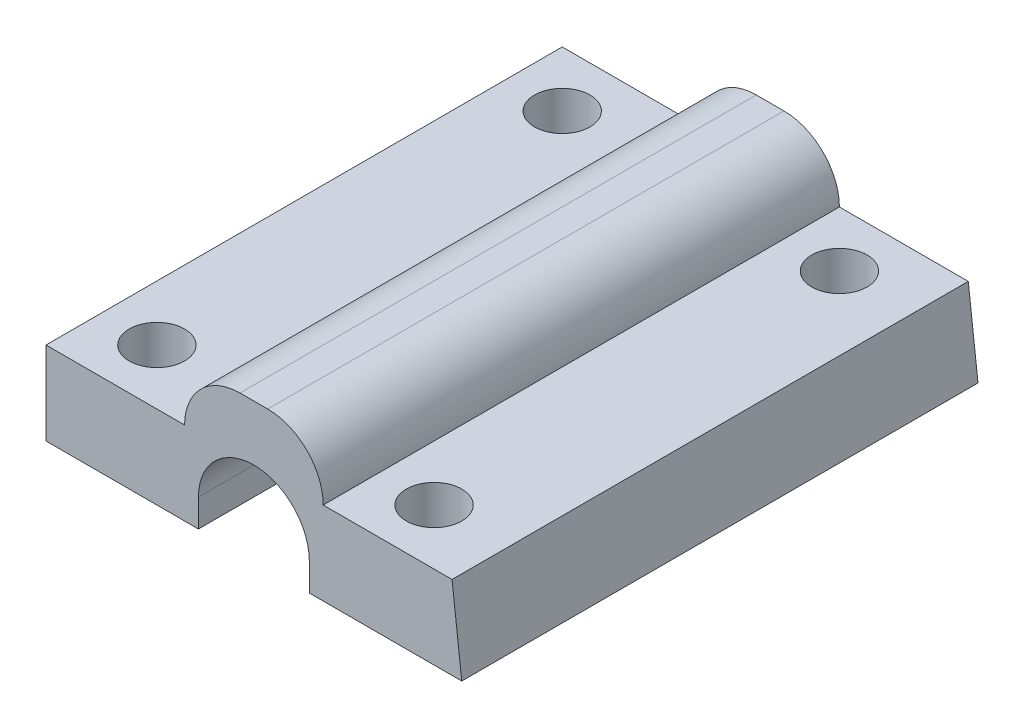
SolidWorks part; units mm, degrees
ref_plane "Front Plane" through (0, 0, 0) normal (0, 0, 1) x (1, 0, 0)
ref_plane "Top Plane" through (0, 0, 0) normal (0, 1, 0) x (1, 0, 0)
ref_plane "Right Plane" through (0, 0, 0) normal (1, 0, 0) x (0, 0, -1)
sketch "Sketch1" plane through (0, 0, 0) normal (0, 1, 0) x (1, 0, 0)
  line L1 (-12.2135, 8.3854) -> (17.7865, 8.3854)
  line L2 (-12.2135, 8.3854) -> (-12.2135, -28.8646)
  line L3 (-12.2135, -28.8646) -> (17.7865, -28.8646)
  line L4 (17.7865, 8.3854) -> (17.7865, -28.8646)
  dimension "D1" = 30
  dimension "D2" = 37.25
extrude "Boss-Extrude1" add sketch "Sketch1" along normal blind 6
sketch "Sketch2" plane through (0, 6, 0) normal (0, 1, 0) x (1, 0, 0)
  line L0 (-12.2135, 8.3854) -> (-12.2135, -28.8646) construction
  line L1 (17.7865, 8.3854) -> (-12.2135, 8.3854) construction
  circle A1 centre (-8.2135, -24.8646) radius 2
  circle A2 centre (11.7865, 4.3854) radius 2
  circle A3 centre (11.7865, -24.8646) radius 2
  circle A4 centre (-8.2135, 4.3854) radius 2
  dimension "D1" = 4
  dimension "D5" = 4
  dimension "D2" = 4
  dimension "D3" = 20
  dimension "D4" = 29.25
  dimension "D6" = 4
  dimension "D7" = 20
  dimension "D8" = 29.25
extrude "Cut-Extrude1" cut sketch "Sketch2" against normal blind 6
sketch "Sketch3" plane through (0, 6, 0) normal (0, 1, 0) x (1, 0, 0)
  line L0 (17.7865, 8.3854) -> (-12.2135, 8.3854) construction
  line L1 (-2.2135, 8.3854) -> (7.7865, 8.3854)
  line L2 (-2.2135, 8.3854) -> (-2.2135, -28.8646)
  line L3 (-2.2135, -28.8646) -> (7.7865, -28.8646)
  line L4 (7.7865, 8.3854) -> (7.7865, -28.8646)
  line L5 (-12.2135, -28.8646) -> (17.7865, -28.8646) construction
  line L6 (-12.2135, 8.3854) -> (-12.2135, -28.8646) construction
  line L7 (17.7865, -28.8646) -> (17.7865, 8.3854) construction
  dimension "D1" = 10
  dimension "D2" = 10
extrude "Boss-Extrude2" add sketch "Sketch3" along normal blind 4
sketch "Sketch4" plane through (0, 0, 0) normal (0, -1, 0) x (1, 0, 0)
  line L0 (-12.2135, 28.8646) -> (17.7865, 28.8646) construction
  line L1 (-1.2135, 28.8646) -> (6.7865, 28.8646)
  line L2 (-1.2135, 28.8646) -> (-1.2135, -8.3854)
  line L3 (-1.2135, -8.3854) -> (6.7865, -8.3854)
  line L4 (6.7865, 28.8646) -> (6.7865, -8.3854)
  line L5 (-12.2135, -8.3854) -> (-12.2135, 28.8646) construction
  line L6 (17.7865, 28.8646) -> (17.7865, -8.3854) construction
  dimension "D1" = 11
  dimension "D2" = 11
extrude "Cut-Extrude2" cut sketch "Sketch4" against normal blind 6
fillet "Fillet2" radius 4 2 edges at (6.7865, 6, 10.2396) (-1.2135, 6, 10.2396)
fillet "Fillet3" radius 4 2 edges at (7.7865, 10, 10.2396) (-2.2135, 10, 10.2396)
sketch "Sketch5" plane through (0, 0, -8.3854) normal (0, 0, -1) x (-1, 0, 0)
  line L0 (-17.7865, 0) -> (-17.0859, 6)
  line L1 (-17.7865, 6) -> (-7.7865, 6) construction
  line L2 (-17.0859, 6) -> (-17.7865, 6)
  line L3 (-17.7865, 6) -> (-17.7865, 0)
extrude "Cut-Extrude3" cut sketch "Sketch5" against normal blind 50
